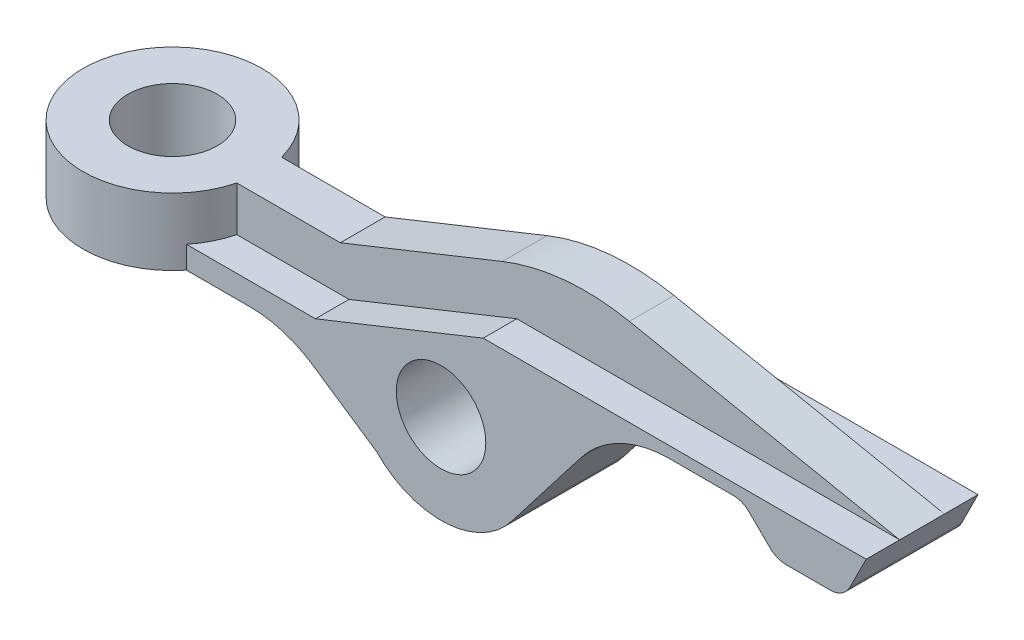
SolidWorks part; units mm, degrees
ref_plane "Plan1" through (0, 0, 0) normal (0, 0, 1) x (1, 0, 0)
ref_plane "Plan2" through (0, 0, 0) normal (0, 1, 0) x (1, 0, 0)
ref_plane "Plan3" through (0, 0, 0) normal (1, 0, 0) x (0, 0, -1)
sketch "Esquisse1" plane through (0, 0, 0) normal (0, 0, 1) x (1, 0, 0)
  line L0 (-5.6148, 1) -> (-12, 1)
  line L1 (19, 4) -> (6.915, 6.417)
  line L2 (1.2399, 5.896) -> (-6, 3)
  line L3 (-6, 3) -> (-12, 3)
  line L4 (1.8852, 4) -> (-5.6148, 1)
  line L5 (-12, 3) -> (-12, 1)
  line L6 (19, 4) -> (1.8852, 4)
  arc A0 (6.915, 6.417) -> (1.2399, 5.896) centre (4.9538, -3.3888) ccw
  point P10 (4, 7)
  dimension "D9" = 10
  dimension "D1" = 19
  dimension "D2" = 4
  dimension "D3" = 7
  dimension "D4" = 4
  dimension "D5" = 3
  dimension "D6" = 6
  dimension "D7" = 12
  dimension "D8" = 2
extrude "Base-Extrusion" add sketch "Esquisse1" along normal mid plane 2
sketch "Esquisse2" plane through (0, 0, 0) normal (0, 0, 1) x (1, 0, 0)
  line L0 (3.2359, -2.3514) -> (6.2512, 1.5551)
  line L1 (10.2093, 3.5) -> (13.0705, 3.5)
  line L2 (15.4105, 2) -> (17.382, 2)
  line L3 (13.7732, 3.2115) -> (14.7079, 2.2885)
  line L4 (18.2764, 2.5528) -> (19, 4)
  line L5 (19, 4) -> (1.8852, 4)
  line L6 (1.8852, 4) -> (-5.6148, 1)
  line L7 (-5.6148, 1) -> (-12, 1)
  line L8 (-12, 1) -> (-5.6148, 1) construction
  line L9 (-12, 1) -> (-12, 0)
  line L10 (-12, 0) -> (-8.5273, 0)
  line L11 (-5.7334, -0.8535) -> (-2.8795, -2.7765)
  arc A0 (-2.8795, -2.7765) -> (3.2359, -2.3514) centre (0, 0) ccw
  arc A1 (10.2093, 3.5) -> (6.2512, 1.5551) centre (10.2093, -1.5) ccw
  arc A2 (13.7732, 3.2115) -> (13.0705, 3.5) centre (13.0705, 2.5) ccw
  arc A3 (15.4105, 2) -> (14.7079, 2.2885) centre (15.4105, 3) cw
  arc A4 (18.2764, 2.5528) -> (17.382, 2) centre (17.382, 3) cw
  arc A5 (-8.5273, 0) -> (-5.7334, -0.8535) centre (-8.5273, -5) cw
  dimension "D1" = 8
  dimension "D3" = 5
  dimension "D4" = 1
  dimension "D5" = 5
  dimension "D2" = 3.5
extrude "Boss.-Extru.1" add sketch "Esquisse2" along normal mid plane 5
sketch "Esquisse3" plane through (0, 0, 0) normal (0, -1, 0) x (1, 0, 0)
  circle A0 centre (-14.5, 0) radius 2
  circle A1 centre (-14.5, 0) radius 4
  dimension "D1" = 14.5
  dimension "D2" = 8
  dimension "D3" = 4
extrude "Boss.-Extru.2" add sketch "Esquisse3" against normal blind 3
sketch "Esquisse4" plane through (0, 0, -2.5) normal (0, 0, -1) x (-1, 0, 0)
  circle A0 centre (0, 0) radius 2
  dimension "D1" = 4
extrude "Enlèv. mat.-Extru.1" cut sketch "Esquisse4" against normal through all
ref_axis "Axe1" through (-14.5, 3, 0) along (0, -1, 0)
ref_plane "Plan4" through (0, 0, 0) normal (0, -1, 0) x (-1, 0, 0)
